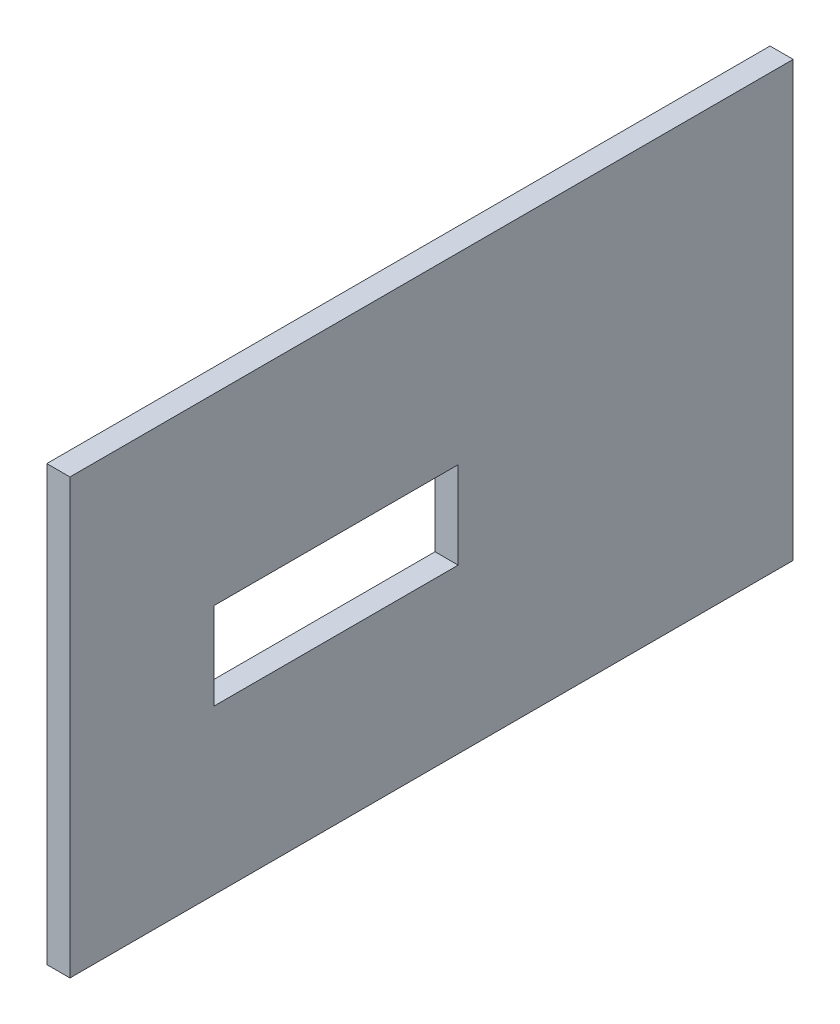
SolidWorks part; units mm, degrees
ref_plane "Front Plane" through (0, 0, 0) normal (0, 0, 1) x (1, 0, 0)
ref_plane "Top Plane" through (0, 0, 0) normal (0, 1, 0) x (1, 0, 0)
ref_plane "Right Plane" through (0, 0, 0) normal (1, 0, 0) x (0, 0, -1)
sketch "Sketch2" plane through (0, 0, 0) normal (1, 0, 0) x (0, 0, -1)
  line L1 (-101.0636, 37.4) -> (-1.0636, 37.4)
  line L2 (-101.0636, 37.4) -> (-101.0636, -22.6)
  line L3 (-101.0636, -22.6) -> (-1.0636, -22.6)
  line L4 (-1.0636, 37.4) -> (-1.0636, -22.6)
  line L5 (-101.0636, 37.4) -> (-1.0636, -22.6) construction
  line L6 (-101.0636, -22.6) -> (-1.0636, 37.4) construction
  point P0 (-51.0636, 7.4)
  dimension "D1" = 60
  dimension "D2" = 100
extrude "Boss-Extrude1" add sketch "Sketch2" along normal blind 3.2
sketch "Sketch3" plane through (3.2, 0, 0) normal (1, 0, 0) x (0, 0, -1)
  line L1 (-81.1637, 12.0312) -> (-47.3877, 12.0312)
  line L2 (-81.1637, 12.0312) -> (-81.1637, 0)
  line L3 (-81.1637, 0) -> (-47.3877, 0)
  line L4 (-47.3877, 12.0312) -> (-47.3877, 0)
  line L5 (-81.1637, 12.0312) -> (-47.3877, 0) construction
  line L6 (-81.1637, 0) -> (-47.3877, 12.0312) construction
  point P0 (-64.2757, 6.0156)
extrude "Cut-Extrude1" cut sketch "Sketch3" against normal blind 3.2
